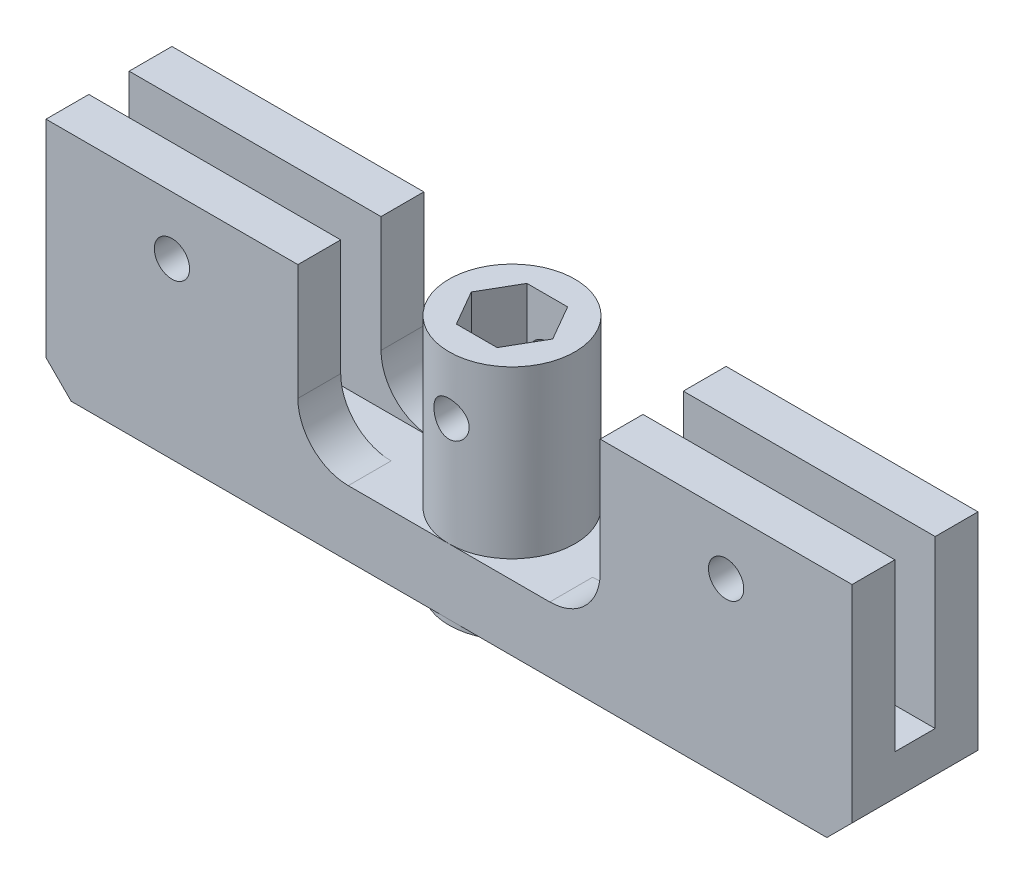
SolidWorks part; units mm, degrees
ref_plane "Front Plane" through (0, 0, 0) normal (0, 0, 1) x (1, 0, 0)
ref_plane "Top Plane" through (0, 0, 0) normal (0, 1, 0) x (1, 0, 0)
ref_plane "Right Plane" through (0, 0, 0) normal (1, 0, 0) x (0, 0, -1)
sketch "Sketch1" plane through (0, 0, 0) normal (0, 1, 0) x (1, 0, 0)
  line L1 (4.0415, 0) -> (2.0207, 3.5)
  line L2 (2.0207, 3.5) -> (-2.0207, 3.5)
  line L3 (-2.0207, 3.5) -> (-4.0415, 0)
  line L4 (-4.0415, 0) -> (-2.0207, -3.5)
  line L5 (-2.0207, -3.5) -> (2.0207, -3.5)
  line L6 (2.0207, -3.5) -> (4.0415, 0)
  circle A0 centre (0, 0) radius 6.25
  circle A1 centre (0, 0) radius 3.5 construction
  dimension "D1" = 12.5
  dimension "D2" = 7
extrude "Boss-Extrude1" add sketch "Sketch1" along normal blind 24
ref_plane "Plane1" through (0, 17.746, 0) normal (0, -1, 0) x (-1, 0, 0)
sketch "Sketch2" plane through (0, 0, 0) normal (0, 0, 1) x (1, 0, 0)
  line L0 (-6.875, 17.746) -> (6.875, 17.746) construction
  circle A0 centre (0, 17.746) radius 1.75
  dimension "D1" = 3.5
extrude "Cut-Extrude2" cut sketch "Sketch2" against normal mid plane 15
sketch "Sketch3" plane through (0, 0, 0) normal (0, -1, 0) x (1, 0, 0)
  line L1 (-40, -6.25) -> (40, -6.25)
  line L2 (-40, -6.25) -> (-40, 6.25)
  line L3 (-40, 6.25) -> (40, 6.25)
  line L4 (40, -6.25) -> (40, 6.25)
  line L5 (-40, -6.25) -> (40, 6.25) construction
  line L6 (-40, 6.25) -> (40, -6.25) construction
  circle A0 centre (0, 0) radius 6.25 construction
  point P0 (0, 0)
  dimension "D1" = 80
extrude "Boss-Extrude2" add sketch "Sketch3" against normal blind 7.5
sketch "Sketch4" plane through (0, 7.5, 0) normal (0, 1, 0) x (1, 0, 0)
  line L6 (-2.0207, -3.5) -> (2.0207, -3.5)
  line L7 (2.0207, -3.5) -> (4.0415, 0)
  line L8 (4.0415, 0) -> (2.0207, 3.5)
  line L9 (2.0207, 3.5) -> (-2.0207, 3.5)
  line L10 (-2.0207, 3.5) -> (-4.0415, 0)
  line L11 (-4.0415, 0) -> (-2.0207, -3.5)
  line L12 (-2.0207, -3.5) -> (2.0207, -3.5)
  line L13 (2.0207, -3.5) -> (4.0415, 0)
  line L14 (4.0415, 0) -> (2.0207, 3.5)
  line L15 (2.0207, 3.5) -> (-2.0207, 3.5)
  line L16 (-2.0207, 3.5) -> (-4.0415, 0)
  line L17 (-4.0415, 0) -> (-2.0207, -3.5)
  dimension "D1" = 0
extrude "Cut-Extrude3" cut sketch "Sketch4" against normal through all
sketch "Sketch5" plane through (0, 0, 0) normal (0, -1, 0) x (1, 0, 0)
  line L4 (-40, 6.25) -> (-40, -6.25)
  line L5 (-40, -6.25) -> (40, -6.25)
  line L6 (40, -6.25) -> (40, 6.25)
  line L7 (40, 6.25) -> (-40, 6.25)
  line L8 (-40, 6.25) -> (-40, -6.25)
  line L9 (-40, -6.25) -> (40, -6.25)
  line L10 (40, -6.25) -> (40, 6.25)
  line L11 (40, 6.25) -> (-40, 6.25)
  dimension "D1" = 0
extrude "Cut-Extrude4" cut sketch "Sketch5" against normal blind 1
sketch "Sketch6" plane through (0, 24, 0) normal (0, 1, 0) x (1, 0, 0)
  line L0 (-2.0207, 3.5) -> (-4.0415, 0) construction
  line L1 (-2.0207, 3.5) -> (-4.0415, 0)
  line L2 (4.0415, 0) -> (2.0207, 3.5) construction
  line L3 (4.0415, 0) -> (2.0207, 3.5)
  line L4 (2.0207, 3.5) -> (-2.0207, 3.5) construction
  line L5 (2.0207, 3.5) -> (-2.0207, 3.5)
  line L6 (2.0207, -3.5) -> (4.0415, 0) construction
  line L7 (2.0207, -3.5) -> (4.0415, 0)
  line L8 (-2.0207, -3.5) -> (2.0207, -3.5) construction
  line L9 (-2.0207, -3.5) -> (2.0207, -3.5)
  line L10 (-4.0415, 0) -> (-2.0207, -3.5) construction
  line L11 (-4.0415, 0) -> (-2.0207, -3.5)
  circle A1 centre (0, 0) radius 6.25
  circle A2 centre (0, 0) radius 6.25
  dimension "D1" = 0
extrude "Boss-Extrude3" add sketch "Sketch6" against normal blind 23.5
sketch "Sketch7" plane through (0, 7.5, 0) normal (0, 1, 0) x (1, 0, 0)
  line L1 (-40, 6.25) -> (-15, 6.25)
  line L2 (-40, 6.25) -> (-40, 2)
  line L3 (-40, 2) -> (-15, 2)
  line L4 (-15, 6.25) -> (-15, 2)
  line L5 (-40, -6.25) -> (-15, -6.25)
  line L6 (-40, -6.25) -> (-40, -2)
  line L7 (-40, -2) -> (-15, -2)
  line L8 (-15, -6.25) -> (-15, -2)
  dimension "D1" = 4
  dimension "D2" = 25
extrude "Boss-Extrude4" add sketch "Sketch7" along normal up to surface (16.5 mm away) up to face at (0, 24, 6.25)
mirror "Mirror1" about plane through (0, 0, 0) normal (1, 0, 0) of "Boss-Extrude4"
fillet "Fillet1" radius 5 4 edges at (-15, 7.5, 4.125) (15, 7.5, 4.125) (15, 7.5, -4.125) (-15, 7.5, -4.125)
ref_plane "Plane2" through (0, 18.246, 0) normal (0, -1, 0) x (-1, 0, 0)
sketch "Sketch8" plane through (0, 0, 0) normal (0, 0, 1) x (1, 0, 0)
  line L0 (-6.875, 18.246) -> (6.875, 18.246) construction
  circle A0 centre (0, 18.246) radius 1.75
  dimension "D1" = 3.5
extrude "Cut-Extrude5" cut sketch "Sketch8" against normal mid plane 15
pattern_linear "LPattern1" count 2 spacing 27.5 along (1, 0, 0) count 2 spacing 27.5 along (-1, 0, 0) of "Cut-Extrude5"
chamfer "Chamfer1" distance 2.5 angle 45 2 edges at (40, 1, 0) (-40, 1, 0)
